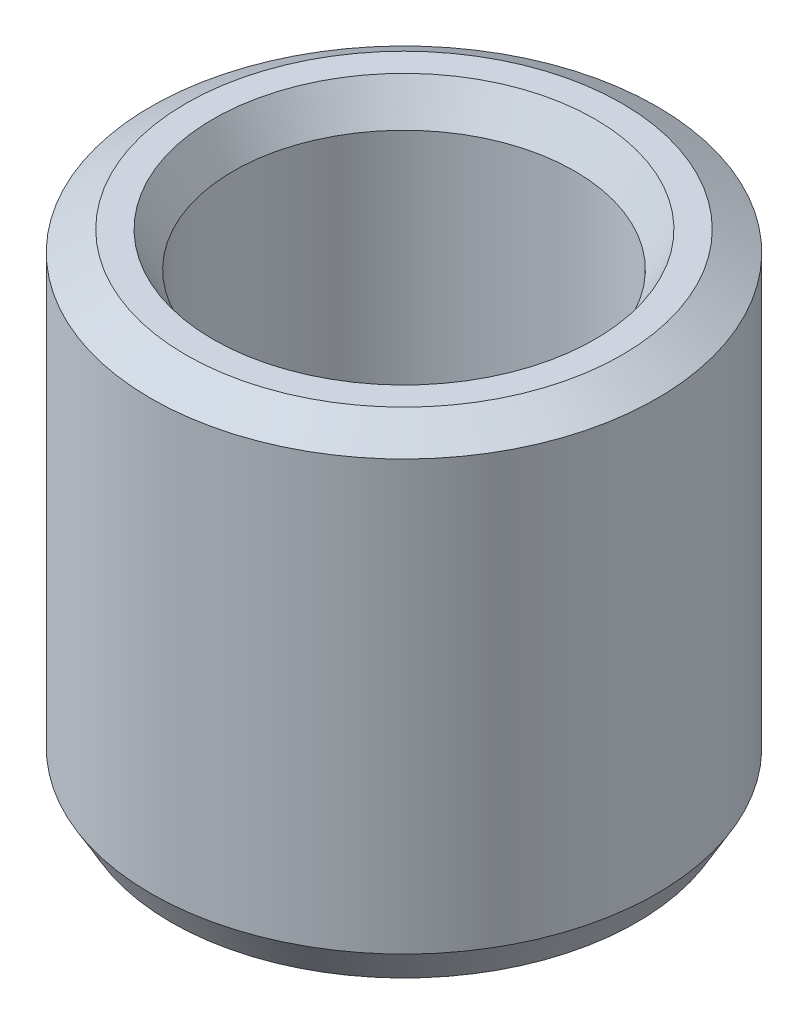
SolidWorks part; units mm, degrees
ref_plane "Front Plane" through (0, 0, 0) normal (0, 0, 1) x (1, 0, 0)
ref_plane "Top Plane" through (0, 0, 0) normal (0, 1, 0) x (1, 0, 0)
ref_plane "Right Plane" through (0, 0, 0) normal (1, 0, 0) x (0, 0, -1)
sketch "Sketch1" plane through (0, 0, 0) normal (0, 1, 0) x (1, 0, 0)
  circle A0 centre (0, 0) radius 32.5
  dimension "SLEEVE_OD" = 65
extrude "Boss-Extrude1" add sketch "Sketch1" along normal blind 62.1742
sketch "Sketch2" plane through (0, 0, 0) normal (0, 1, 0) x (1, 0, 0)
  circle A0 centre (0, 0) radius 21.9295
  dimension "BORE_D" = 43.8589
extrude "Cut-Extrude1" cut sketch "Sketch2" along normal through all
chamfer "Chamfer1" distance 2.5952 angle 60 4 edges at (0, 62.1742, 21.9295) (0, 0, 21.9295) (0, 0, 32.5) (0, 62.1742, 32.5) first distance on face at (0, 62.1742, 21.9295) first distance on face at (0, 0, 21.9295) first distance on face at (0, 62.1742, 32.5)
